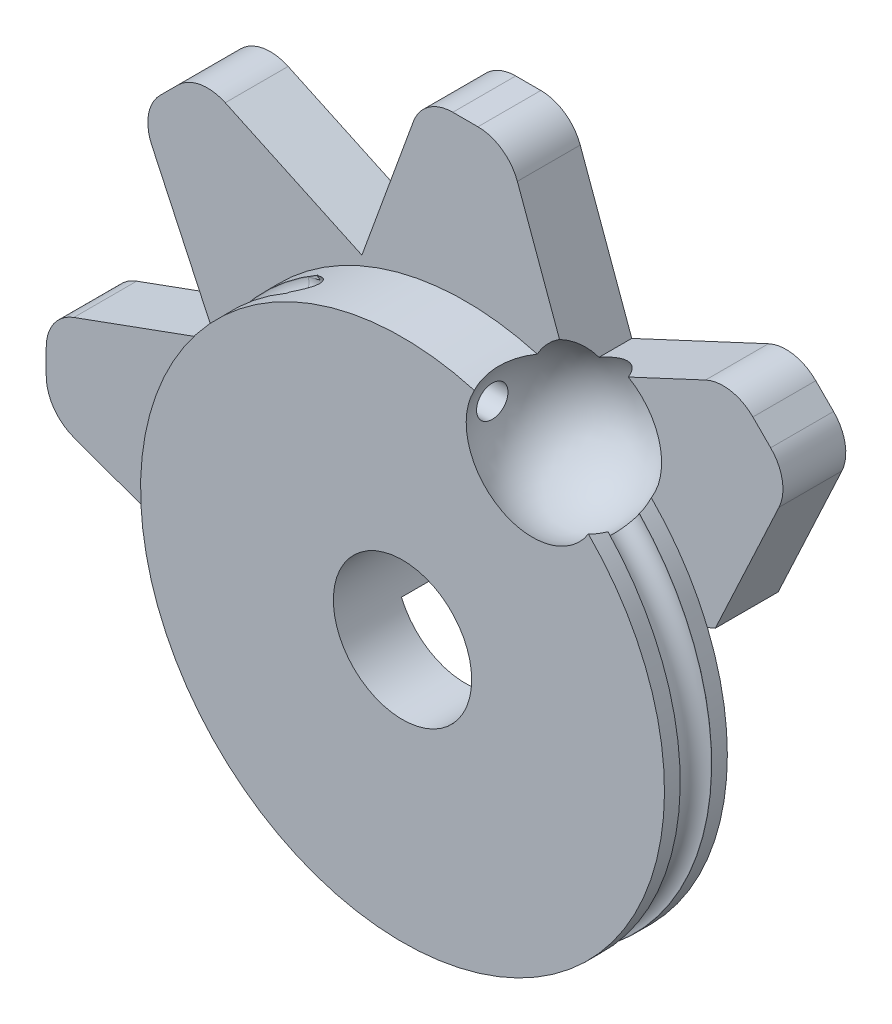
SolidWorks part; units mm, degrees
ref_plane "Front Plane" through (0, 0, 0) normal (0, 0, 1) x (1, 0, 0)
ref_plane "Top Plane" through (0, 0, 0) normal (0, 1, 0) x (1, 0, 0)
ref_plane "Right Plane" through (0, 0, 0) normal (1, 0, 0) x (0, 0, -1)
ref_axis "Axis1" through (-10.8788, 0, 0) along (1, 0, 0)
ref_axis "Axis2" through (0, 0, 2.0438) along (0, 0, -1)
ref_plane "Plane5" through (0, 0, 0) normal (0.866, 0.5, 0) x (0, 0, -1)
ref_plane "Plane6" through (3.1, 0, 0) normal (1, 0, 0) x (0, 0, -1)
sketch "Sketch1" plane through (0, 0, 0) normal (0, 0, 1) x (1, 0, 0)
  line L0 (-10.8788, 0) -> (8.4547, 0) construction
  circle A0 centre (0, 0) radius 6.25
  dimension "D1" = 12.5
extrude "body" add sketch "Sketch1" along normal blind 1.5 contours A0
sketch "Sketch2" plane through (0, 0, 0) normal (1, 0, 0) x (0, 0, -1)
  line L1 (0, 6.25) -> (-1.5, 6.25) construction
  line L2 (0, 5.25) -> (-1.5, 5.25) construction
  line L3 (-0.75, 5.25) -> (-0.75, -4.75) construction
  line L4 (0, -6.25) -> (0, 6.25) construction
  line L5 (0, -6.25) -> (0, 6.25) construction
  circle A0 centre (-0.75, 5.25) radius 0.375
  circle A1 centre (-0.75, -4.75) radius 0.375
  dimension "D1" = 0.75
  dimension "D3" = 0.75
  dimension "D4" = 1.5
  dimension "D2" = 1
extrude "Hole to trap cable knot" cut sketch "Sketch2" against normal through all and the other way blind 10 contours A0 | A1
ref_plane "Plane1" through (0, 0, 1.875) normal (0, 0, 1) x (1, 0, 0)
sketch "Sketch6" plane through (0, 0, 1.875) normal (0, 0, 1) x (1, 0, 0)
  line L0 (1.0209, -1.7683) -> (-1.0209, 1.7683) construction
  arc A0 (3.9111, 4.875) -> (2.7243, 5.625) centre (0, 0) ccw construction
  circle A2 centre (0, 0) radius 6.25 construction
  arc A3 (-3.125, 5.4127) -> (3.2608, 5.332) centre (0, 0) ccw
  arc A4 (3.9111, 4.875) -> (2.7243, 5.625) centre (0, 0) ccw construction
sketch "Sketch10" plane through (-5.4127, 9.375, 0) normal (-0.866, -0.5, 0) x (-0.5, 0.866, 0)
  line L0 (-4.5831, -1.125) -> (-3.8727, -1.125)
  line L1 (-3.8727, -1.125) -> (-3.8727, -0.3748)
  line L2 (-3.8727, -0.3748) -> (-4.5831, -0.3748)
  arc A0 (-4.5831, -0.3748) -> (-4.5831, -1.125) centre (-4.5831, -0.7499) ccw
  spline S0 degree 3 poles (-4.5903, -1.125) (-4.5759, -1.125) (-4.5739, -1.1025) (-4.5775, -1.0318) (-4.5799, -1.0018) (-4.5843, -0.9422) (-4.5859, -0.9199) (-4.589, -0.8665) (-4.5904, -0.8353) (-4.592, -0.7664) (-4.5919, -0.7281) (-4.5902, -0.6593) (-4.5887, -0.6289) (-4.5841, -0.5506) (-4.5809, -0.5129) (-4.5744, -0.422) (-4.574, -0.3902) (-4.5837, -0.3678) (-4.5938, -0.3778) (-4.6147, -0.4453) (-4.6227, -0.4771) (-4.6376, -0.5669) (-4.6447, -0.6281) (-4.6494, -0.7694) (-4.6461, -0.8461) (-4.6338, -0.9631) (-4.6257, -1.0065) (-4.603, -1.1026) (-4.5903, -1.125) (-4.5759, -1.125) (-4.5739, -1.1025) knots -0.125 -0.125 0 0 0.125 0.125 0.1875 0.1875 0.21875 0.21875 0.25 0.25 0.28125 0.28125 0.3125 0.3125 0.375 0.375 0.5 0.5 0.625 0.625 0.6875 0.6875 0.75 0.75 0.8125 0.8125 0.875 0.875 1 1 1.125 1.125 1.1875 only from (-4.5831, -1.125) to (-4.5831, -1.125) construction
  spline S1 degree 3 poles (-4.5903, -1.125) (-4.5759, -1.125) (-4.5739, -1.1025) (-4.5775, -1.0318) (-4.5799, -1.0018) (-4.5843, -0.9422) (-4.5859, -0.9199) (-4.589, -0.8665) (-4.5904, -0.8353) (-4.592, -0.7664) (-4.5919, -0.7281) (-4.5902, -0.6593) (-4.5887, -0.6289) (-4.5841, -0.5506) (-4.5809, -0.5129) (-4.5744, -0.422) (-4.574, -0.3902) (-4.5837, -0.3678) (-4.5938, -0.3778) (-4.6147, -0.4453) (-4.6227, -0.4771) (-4.6376, -0.5669) (-4.6447, -0.6281) (-4.6494, -0.7694) (-4.6461, -0.8461) (-4.6338, -0.9631) (-4.6257, -1.0065) (-4.603, -1.1026) (-4.5903, -1.125) (-4.5759, -1.125) (-4.5739, -1.1025) knots -0.125 -0.125 0 0 0.125 0.125 0.1875 0.1875 0.21875 0.21875 0.25 0.25 0.28125 0.28125 0.3125 0.3125 0.375 0.375 0.5 0.5 0.625 0.625 0.6875 0.6875 0.75 0.75 0.8125 0.8125 0.875 0.875 1 1 1.125 1.125 1.1875 only from (-4.5831, -1.125) to (-4.5831, -1.125) construction
  point P1 (-4.5831, -0.3748)
sweep "track for cable" cut profiles "Sketch10" path "Sketch6"
sketch "Sketch12" plane through (0, 0, 0) normal (0, 0, -1) x (-1, 0, 0)
  line L0 (0, 10) -> (0, -10) construction
  line L1 (-2.5653, 5.6993) -> (-1.2395, 9.342)
  line L2 (-0.2998, 10) -> (0.2998, 10)
  line L3 (1.2395, 9.342) -> (2.5653, 5.6993)
  line L6 (-3.2365, 3.8554) -> (3.2365, 3.8554) construction
  line L7 (-2.5653, 5.6993) -> (0, 0)
  line L8 (0, 0) -> (2.5653, 5.6993)
  arc A0 (-1.2395, 9.342) -> (-0.2998, 10) centre (-0.2998, 9) cw
  arc A1 (0.2998, 10) -> (1.2395, 9.342) centre (0.2998, 9) cw
  circle A4 centre (0, 0) radius 6.25 construction
  point P9 (-1, 10)
  point P12 (1, 10)
  dimension "D6" = 1
  dimension "D1" = 20
  dimension "D2" = 2
  dimension "D3" = 6.4729
  dimension "D4" = 110
  dimension "D5" = 110
sketch "Sketch14" plane through (0, 0, 0) normal (0, 0, -1) x (-1, 0, 0)
  line L0 (5.7294, 7.4823) -> (2.4696, 5.9622)
  line L1 (7.2831, 6.8591) -> (6.8591, 7.2831)
  line L2 (5.9622, 2.4696) -> (7.4823, 5.7294)
  line L3 (0, 0) -> (5.844, 2.216) construction
  line L4 (2.216, 5.844) -> (0, 0) construction
  line L5 (-1.2395, 9.342) -> (-2.5653, 5.6993)
  line L6 (0.2998, 10) -> (-0.2998, 10)
  line L7 (2.5653, 5.6993) -> (1.2395, 9.342)
  line L8 (0, 0) -> (2.5653, 5.6993)
  line L9 (0, 0) -> (2.5653, 5.6993) construction
  line L10 (-1.2395, 9.342) -> (-2.4696, 5.9622)
  line L11 (0.2998, 10) -> (-0.2998, 10)
  line L12 (2.4696, 5.9622) -> (1.2395, 9.342)
  line L13 (-2.5653, 5.6993) -> (0, 0)
  line L14 (-2.5653, 5.6993) -> (0, 0) construction
  line L15 (9.342, 1.2395) -> (5.9622, 2.4696)
  line L16 (10, -0.2998) -> (10, 0.2998)
  line L17 (5.9622, -2.4696) -> (9.342, -1.2395)
  line L18 (0, 0) -> (5.6993, -2.5653) construction
  line L19 (5.6993, 2.5653) -> (0, 0) construction
  line L20 (7.4823, -5.7294) -> (5.9622, -2.4696) construction
  line L21 (6.8591, -7.2831) -> (7.2831, -6.8591) construction
  line L22 (2.4696, -5.9622) -> (5.7294, -7.4823) construction
  line L23 (0, 0) -> (2.216, -5.844) construction
  line L24 (5.844, -2.216) -> (0, 0) construction
  line L25 (1.2395, -9.342) -> (2.4696, -5.9622) construction
  line L26 (-0.2998, -10) -> (0.2998, -10) construction
  line L27 (-2.4696, -5.9622) -> (-1.2395, -9.342) construction
  line L28 (0, 0) -> (-2.5653, -5.6993) construction
  line L29 (2.5653, -5.6993) -> (0, 0) construction
  line L30 (-5.7294, -7.4823) -> (-2.4696, -5.9622) construction
  line L31 (-7.2831, -6.8591) -> (-6.8591, -7.2831) construction
  line L32 (-5.9622, -2.4696) -> (-7.4823, -5.7294) construction
  line L33 (0, 0) -> (-5.844, -2.216) construction
  line L34 (-2.216, -5.844) -> (0, 0) construction
  line L35 (-9.342, -1.2395) -> (-5.9622, -2.4696) construction
  line L36 (-10, 0.2998) -> (-10, -0.2998) construction
  line L37 (-5.9622, 2.4696) -> (-9.342, 1.2395) construction
  line L38 (0, 0) -> (-5.6993, 2.5653) construction
  line L39 (-5.6993, -2.5653) -> (0, 0) construction
  line L40 (-7.4823, 5.7294) -> (-5.9622, 2.4696)
  line L41 (-6.8591, 7.2831) -> (-7.2831, 6.8591)
  line L42 (-2.4696, 5.9622) -> (-5.7294, 7.4823)
  line L43 (0, 0) -> (-2.216, 5.844) construction
  line L44 (-5.844, 2.216) -> (0, 0) construction
  line L45 (5.9622, -2.4696) -> (-5.9622, 2.4696)
  arc A0 (6.8591, 7.2831) -> (5.7294, 7.4823) centre (6.152, 6.5759) ccw
  arc A1 (7.4823, 5.7294) -> (7.2831, 6.8591) centre (6.5759, 6.152) ccw
  arc A2 (-0.2998, 10) -> (-1.2395, 9.342) centre (-0.2998, 9) ccw
  arc A3 (1.2395, 9.342) -> (0.2998, 10) centre (0.2998, 9) ccw
  arc A4 (-0.2998, 10) -> (-1.2395, 9.342) centre (-0.2998, 9) ccw
  arc A5 (1.2395, 9.342) -> (0.2998, 10) centre (0.2998, 9) ccw
  arc A6 (10, 0.2998) -> (9.342, 1.2395) centre (9, 0.2998) ccw
  arc A7 (9.342, -1.2395) -> (10, -0.2998) centre (9, -0.2998) ccw
  arc A8 (7.2831, -6.8591) -> (7.4823, -5.7294) centre (6.5759, -6.152) ccw construction
  arc A9 (5.7294, -7.4823) -> (6.8591, -7.2831) centre (6.152, -6.5759) ccw construction
  arc A10 (0.2998, -10) -> (1.2395, -9.342) centre (0.2998, -9) ccw construction
  arc A11 (-1.2395, -9.342) -> (-0.2998, -10) centre (-0.2998, -9) ccw construction
  arc A12 (-6.8591, -7.2831) -> (-5.7294, -7.4823) centre (-6.152, -6.5759) ccw construction
  arc A13 (-7.4823, -5.7294) -> (-7.2831, -6.8591) centre (-6.5759, -6.152) ccw construction
  arc A14 (-10, -0.2998) -> (-9.342, -1.2395) centre (-9, -0.2998) ccw construction
  arc A15 (-9.342, 1.2395) -> (-10, 0.2998) centre (-9, 0.2998) ccw construction
  arc A16 (-7.2831, 6.8591) -> (-7.4823, 5.7294) centre (-6.5759, 6.152) ccw
  arc A17 (-5.7294, 7.4823) -> (-6.8591, 7.2831) centre (-6.152, 6.5759) ccw
  point P67 (0, 0)
  dimension "D1" = 0
  dimension "D2" = 8
extrude "thumb grip" add sketch "Sketch14" along normal blind 1.5
sketch "Sketch13" plane through (0, 0, 1.5) normal (0, 0, 1) x (1, 0, 0)
  circle A0 centre (0, 0) radius 1.65
  dimension "D1" = 3.3
extrude "hole for screw" cut sketch "Sketch13" against normal through all
sketch "Sketch20" plane through (3.1, 0, 0) normal (1, 0, 0) x (0, 0, -1)
  line L0 (-0.75, 7) -> (-0.75, 3.5)
  line L1 (-0.75, 7.7934) -> (-0.75, 1.6513) construction
  circle A0 centre (-0.75, 5.25) radius 1.75 construction
  arc A1 (-0.3841, 5.332) -> (-1.1159, 5.332) centre (-0.75, 5.25) ccw construction
  arc A2 (-0.3841, 5.332) -> (-1.1159, 5.332) centre (-0.75, 5.25) ccw construction
  arc A3 (-0.75, 7) -> (-0.75, 3.5) centre (-0.75, 5.25) cw
  dimension "D1" = 3.5
revolve "trap for ball" cut sketch "Sketch20" angle 360 about L1
sketch "Sketch21" plane through (0, 0, 1.5) normal (0, 0, 1) x (1, 0, 0)
  circle A0 centre (0, 0) radius 2.8716
  circle A3 centre (0, 0) radius 1.65 construction
  circle A4 centre (0, 0) radius 1.65
extrude "lip to contact handle" [suppressed] add sketch "Sketch21" along normal blind 0.25 and the other way blind 3.75
fillet "Fillet1" [suppressed] radius 0.1
equation "\"Do\"=8.5mm"
equation "\"Lo\"=10"
equation "\"screw_diam\" = 3.5mm"
equation "\"wheel_Do\"=12.5mm"
equation "\"wheel_thickness\"=4mm"
equation "\"Collet_diameter\"=4.3"
equation "\"clearance\"= 0.5mm"
equation "\"D1@Sketch1\"=\"wheel_Do\""
equation "\"wheel_total_diam_ent\"=20"
equation "\"D1@Sketch12\"=\"wheel_total_diam_ent\""
equation "\"handle_body_width\" = 10mm"
equation "\"finger_diameter\"=35"
equation "\"collet_lid_diameter\"=10"
equation "\"screw_cap_diam\"=5.15"
equation "\"handle_thickness\"=12.5mm"
equation "\"post_hole_diam\"=2"
equation "\"roll_rod_diam\"= 6.5 "
equation "\"roll_rod_length\"=6.6"
equation "\"disc_diam\"=5"
equation "\"disc_width\"=1.5"
equation "\"arm_width\"=5"
equation "\"arm_thickness\"=4.5"
equation "\"wheel_total_diam\"=30"
equation "\"D1@thumb grip\"=\"wheel_thickness\"-2.5"
equation "\"D1@body\"=\"wheel_thickness\""
